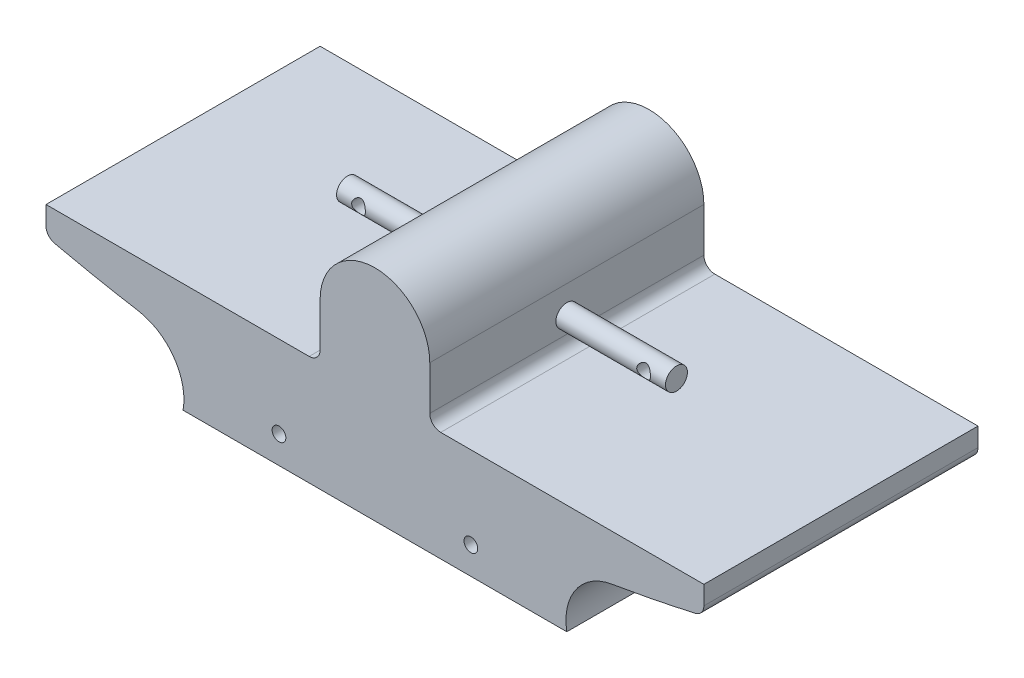
SolidWorks part; units mm, degrees
ref_plane "Front Plane" through (0, 0, 0) normal (0, 0, 1) x (1, 0, 0)
ref_plane "Top Plane" through (0, 0, 0) normal (0, 1, 0) x (1, 0, 0)
ref_plane "Right Plane" through (0, 0, 0) normal (1, 0, 0) x (0, 0, -1)
sketch "Sketch1" plane through (0, 0, 0) normal (0, 0, 1) x (1, 0, 0)
  line L0 (-30, 2.5) -> (30, 2.5)
  line L1 (-30, 2.5) -> (-30, 0)
  line L2 (30, 2.5) -> (30, 0)
  line L3 (0, 2.5) -> (0, -3.5) construction
  line L4 (0, 7.5) -> (0, -3.5) construction
  line L5 (5, 7.5) -> (5, -3.4028)
  line L6 (-5, 7.5) -> (-5, -3.4028)
  line L10 (-17.5, -7.5) -> (17.5, -7.5)
  line L11 (-5, -3.4028) -> (-17.5, -7.5)
  line L12 (5, -3.4028) -> (17.5, -7.5)
  arc A0 (5, 7.5) -> (-5, 7.5) centre (0, 7.5) ccw
  spline S0 degree 2 poles (-30, 0) (0, -7) (30, 0) knots 0 0 0 1 1 1
  dimension "D8" = 5
  dimension "D13" = 7.5
  dimension "D1" = 60
  dimension "D2" = 30
  dimension "D3" = 2.5
  dimension "D4" = 2.5
  dimension "D5" = 2.5
  dimension "D6" = 6
  dimension "D7" = 3.5
  dimension "D9" = 5
  dimension "D10" = 35
  dimension "D11" = 17.5
  dimension "D12" = 4
  dimension "D14" = 10.9028
  dimension "D15" = 5
  dimension "D16" = 13.1544
  dimension "D17" = 10
extrude "Boss-Extrude1" add sketch "Sketch1" along normal mid plane 25
sketch "Sketch15" plane through (5, 0, 0) normal (1, 0, 0) x (0, 0, -1)
  line L0 (-17.984, -0.5) -> (15.3084, -0.5) construction
  circle A0 centre (0, 5) radius 1
  dimension "D1" = 2
  dimension "D2" = 2.5
  dimension "D3" = 12.5
  dimension "D4" = 3
extrude "Boss-Extrude2" add sketch "Sketch15" along normal blind 10
sketch "Sketch19" plane through (0, 0, 0) normal (0, 0, 1) x (1, 0, 0)
  line L0 (-34.7382, -0.5) -> (31.5053, -0.5) construction
  circle A0 centre (13, 5) radius 0.625
  dimension "D1" = 1.25
  dimension "D2" = 1
  dimension "D3" = 2
  dimension "D4" = 3
extrude "Cut-Extrude2" cut sketch "Sketch19" against normal mid plane 2
mirror "Mirror1" about plane through (0, 0, 0) normal (1, 0, 0) of "Cut-Extrude2", "Boss-Extrude2"
fillet "Fillet1" radius 1 4 edges at (-30, 0, 0) (30, 0, 0) (5, 2.5, 0) (-5, 2.5, 0)
fillet "Fillet9" radius 5 2 edges at (5, -3.4028, 0) (-5, -3.4028, 0)
sketch "Sketch32" plane through (0, -7.5, 0) normal (0, -1, 0) x (1, 0, 0)
  line L1 (-15, -10) -> (15, -10)
  line L2 (-15, -10) -> (-15, 10)
  line L3 (-15, 10) -> (15, 10)
  line L4 (15, -10) -> (15, 10)
  line L5 (-15, -10) -> (15, 10) construction
  line L6 (-15, 10) -> (15, -10) construction
  point P1 (0, 0)
  dimension "D1" = 30
  dimension "D2" = 20
extrude "Cut-Extrude10" cut sketch "Sketch32" against normal blind 5
sketch "Sketch34" plane through (0, 0, 0) normal (0, 0, 1) x (1, 0, 0)
  line L0 (0, 0) -> (0, -20.6207) construction
  circle A0 centre (-8.75, -5) radius 0.625
  circle A1 centre (8.75, -5) radius 0.625
  dimension "D1" = 1.25
  dimension "D2" = 8.75
  dimension "D3" = 5
extrude "Cut-Extrude9" cut sketch "Sketch34" against normal mid plane 25
